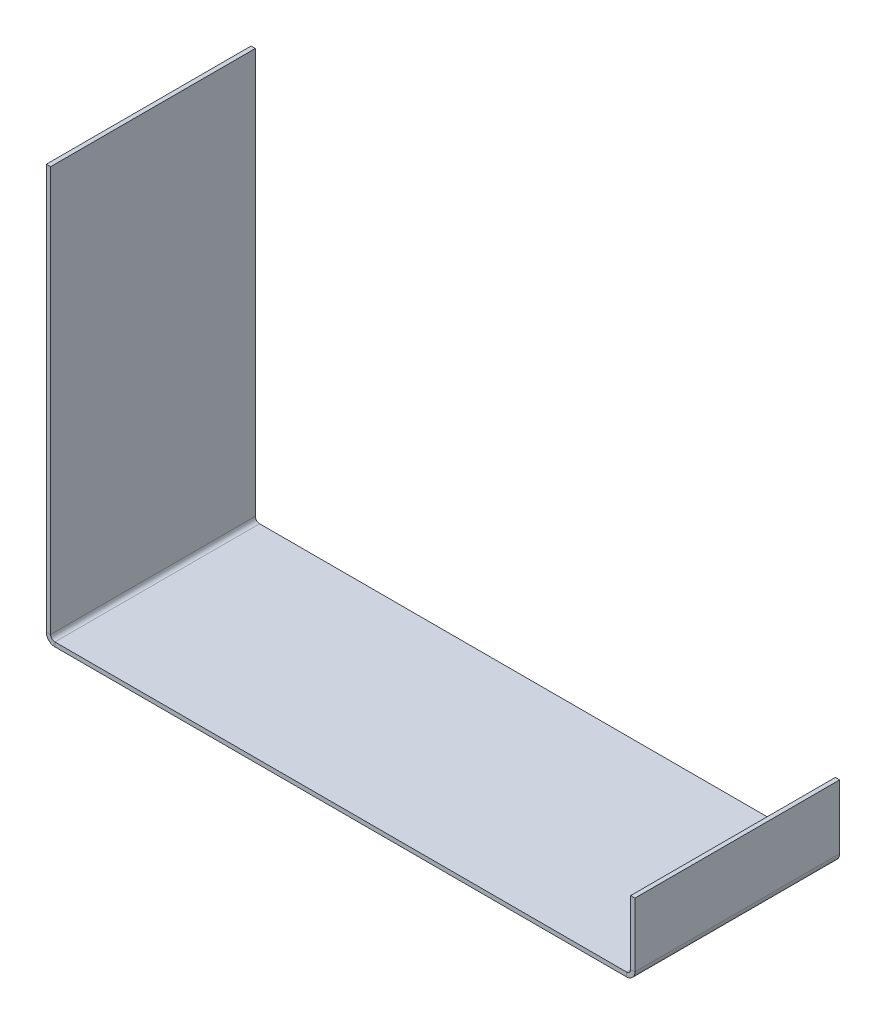
SolidWorks part; units mm, degrees
note: The reader was unsure of these and kept them because the rebuilt part matched: flange length of "Edge-Flange1", "Edge-Flange3".
material "6061-T6 (SS)"
ref_plane "Front Plane" through (0, 0, 0) normal (0, 0, 1) x (1, 0, 0)
ref_plane "Top Plane" through (0, 0, 0) normal (0, 1, 0) x (1, 0, 0)
ref_plane "Right Plane" through (0, 0, 0) normal (1, 0, 0) x (0, 0, -1)
sketch "Sketch1" plane through (0, 0, 0) normal (0, 1, 0) x (1, 0, 0)
  line L1 (-107.95, 38.1) -> (107.95, 38.1)
  line L2 (-107.95, 38.1) -> (-107.95, -38.1)
  line L3 (-107.95, -38.1) -> (107.95, -38.1)
  line L4 (107.95, 38.1) -> (107.95, -38.1)
  line L5 (-107.95, 38.1) -> (107.95, -38.1) construction
  line L6 (-107.95, -38.1) -> (107.95, 38.1) construction
  point P0 (0, 0)
  dimension "D1" = 215.9
  dimension "D2" = 76.2
base flange "Base-Flange1" sketch "Sketch1" thickness 1.5875 reverse thickness direction no parameters "D1"=254
edge flange "Edge-Flange1" sketch "Sketch8" flange angle 90 flange length 152.4 flange position material outside bend radius 1.5875 thickness 1.5875 relief rectangular parameters "D6"=10
sketch "Sketch8" plane through (-107.95, 0, 0) normal (-1, 0, 0) x (0, 0, 1)
  line L2 (-38.1, 0) -> (-38.1, 152.4)
  line L3 (-38.1, 152.4) -> (38.1, 152.4)
  line L4 (38.1, 152.4) -> (38.1, 0)
  line L5 (-38.1, 0) -> (38.1, 0) construction
  line L6 (-38.1, 0) -> (38.1, 0)
bend "EdgeBend1" bend radius 1.5875 bend angle 90 parameters "D5"=1
edge flange "Edge-Flange3" sketch "Sketch12" flange angle 90 flange length 25.4 flange position material outside bend radius 1.5875 thickness 1.5875 relief rectangular parameters "D6"=10
sketch "Sketch12" plane through (107.95, 0, 0) normal (1, 0, 0) x (0, 0, -1)
  line L2 (-38.1, 0) -> (-38.1, 25.4)
  line L3 (-38.1, 25.4) -> (38.1, 25.4)
  line L4 (38.1, 25.4) -> (38.1, 0)
  line L7 (-38.1, 0) -> (38.1, 0) construction
  line L8 (-38.1, 0) -> (38.1, 0)
bend "EdgeBend2" bend radius 1.5875 bend angle 90 parameters "D5"=2
sketch "Bend-Lines1" [suppressed] plane through (0, 0, 0) normal (0, 1, 0) x (1, 0, 0)
sketch "Bounding-Box1" [suppressed] plane through (0, 0, 0) normal (0, 1, 0) x (1, 0, 0)
sheet metal parameters "Sheet-Metal1" thickness 1.5875 parameters "D1"=254
flat pattern "Flat-Pattern1" [suppressed]
sketch "Bend-Lines2" plane through (0, 0, 0) normal (0, 1, 0) x (1, 0, 0)
sketch3d "Bounding-Box2" [suppressed]
  line L0 (-101.6, -38.1, 0) -> (101.6, -38.1, 0) construction
  line L1 (-101.6, 38.1, 0) -> (101.6, 38.1, 0) construction
  line L2 (-101.6, -38.1, 0) -> (-101.6, 38.1, 0) construction
  line L3 (101.6, -38.1, 0) -> (101.6, 38.1, 0) construction
sheet metal parameters "Sheet-Metal2" thickness 1.5875 parameters "D1"=254
flat pattern "Flat-Pattern1"
sketch "Bend-Lines2" plane through (0, 0, 0) normal (0, 1, 0) x (1, 0, 0)
  line L0 (-101.8827, 38.1) -> (-101.8827, -38.1) construction
  line L1 (-101.8827, 38.1) -> (-101.8827, -38.1) construction
sketch3d "Bounding-Box2" [suppressed]
  line L0 (101.6, -38.1, 0) -> (-254.5655, -38.1, 0) construction
  line L1 (101.6, 38.1, 0) -> (-254.5655, 38.1, 0) construction
  line L2 (101.6, -38.1, 0) -> (101.6, 38.1, 0) construction
  line L3 (-254.5655, -38.1, 0) -> (-254.5655, 38.1, 0) construction
bend of the flat pattern "Flatten-<EdgeBend1>1"
sheet metal parameters "Sheet-Metal3" thickness 1.5875 parameters "D1"=254
flat pattern "Flat-Pattern1"
sketch "Bend-Lines2" plane through (0, 0, 0) normal (0, 1, 0) x (1, 0, 0)
  line L0 (-108.2327, 38.1) -> (-108.2327, -38.1) construction
  line L1 (-108.2327, 38.1) -> (-108.2327, -38.1) construction
  line L2 (108.2327, -38.1) -> (108.2327, 38.1) construction
  line L3 (108.2327, -38.1) -> (108.2327, 38.1) construction
sketch3d "Bounding-Box2" [suppressed]
  line L0 (133.9155, -38.1, 0) -> (-260.9155, -38.1, 0) construction
  line L1 (133.9155, 38.1, 0) -> (-260.9155, 38.1, 0) construction
  line L2 (133.9155, -38.1, 0) -> (133.9155, 38.1, 0) construction
  line L3 (-260.9155, -38.1, 0) -> (-260.9155, 38.1, 0) construction
bend of the flat pattern "Flatten-<EdgeBend1>1"
bend of the flat pattern "Flatten-<EdgeBend2>1"
